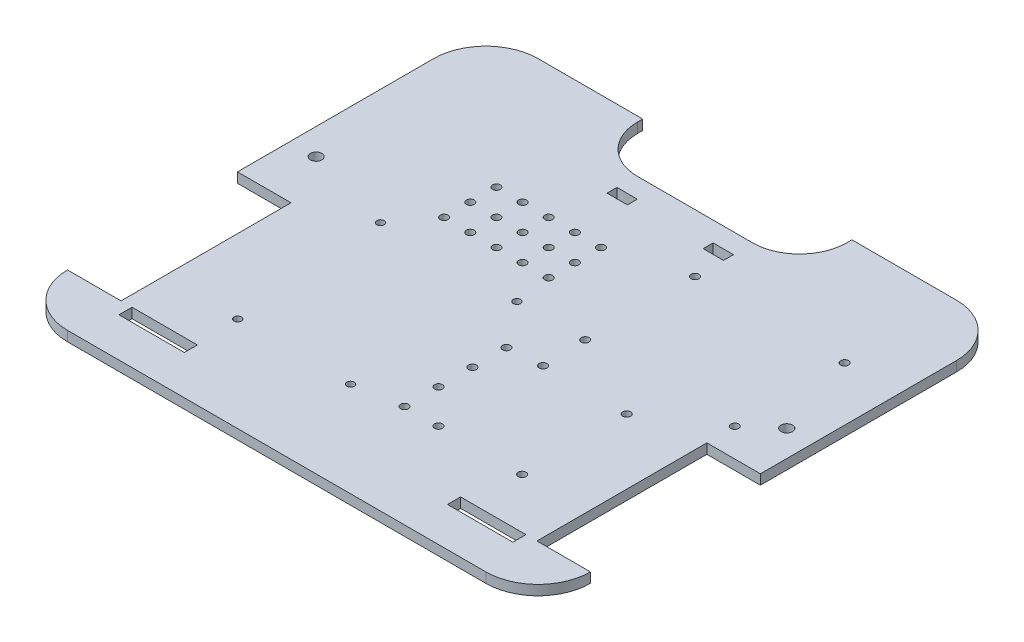
SolidWorks part; units mm, degrees
ref_plane "Front Plane" through (0, 0, 0) normal (0, 0, 1) x (1, 0, 0)
ref_plane "Top Plane" through (0, 0, 0) normal (0, 1, 0) x (1, 0, 0)
ref_plane "Right Plane" through (0, 0, 0) normal (1, 0, 0) x (0, 0, -1)
sketch "Sketch1" plane through (0, 0, 0) normal (0, 1, 0) x (1, 0, 0)
  line L1 (-127, 114.3) -> (127, 114.3)
  line L2 (-127, 114.3) -> (-127, -114.3)
  line L3 (-127, -114.3) -> (127, -114.3)
  line L4 (127, 114.3) -> (127, -114.3)
  line L5 (-127, 114.3) -> (127, -114.3) construction
  line L6 (-127, -114.3) -> (127, 114.3) construction
  point P0 (0, 0)
  dimension "D1" = 254
  dimension "D2" = 228.6
extrude "Boss-Extrude1" add sketch "Sketch1" along normal blind 4.826
sketch "Sketch2" plane through (0, 4.826, 0) normal (0, 1, 0) x (1, 0, 0)
  line L0 (-127, 114.3) -> (-127, -114.3) construction
  line L1 (-127, -6.35) -> (-101, -6.35)
  line L2 (-127, -6.35) -> (-127, -88.9)
  line L3 (-127, -88.9) -> (-101, -88.9)
  line L4 (-101, -6.35) -> (-101, -88.9)
  line L5 (127, -114.3) -> (127, 114.3) construction
  line L6 (127, -6.35) -> (101, -6.35)
  line L7 (127, -6.35) -> (127, -88.9)
  line L8 (127, -88.9) -> (101, -88.9)
  line L9 (101, -6.35) -> (101, -88.9)
  line L10 (-127, -114.3) -> (127, -114.3) construction
  dimension "D1" = 25.4
  dimension "D2" = 25.4
  dimension "D3" = 82.55
  dimension "D4" = 82.55
  dimension "D5" = 26
  dimension "D6" = 26
extrude "Cut-Extrude1" cut sketch "Sketch2" against normal blind 4.826
sketch "Sketch4" plane through (0, 4.826, 0) normal (0, 1, 0) x (1, 0, 0)
  line L0 (0, -114.3) -> (0, 114.3) construction
  line L1 (-127, -114.3) -> (127, -114.3) construction
  line L2 (127, 114.3) -> (-127, 114.3) construction
  line L3 (-127, 88.9) -> (-101.6, 88.9) construction
  line L4 (-127, 114.3) -> (-127, -6.35) construction
  line L5 (-101.6, 88.9) -> (-101.6, 114.3) construction
  line L6 (-127, 88.9) -> (-127, 114.3)
  line L7 (-127, 114.3) -> (-101.6, 114.3)
  line L8 (127, 88.9) -> (127, 114.3)
  line L9 (127, 114.3) -> (101.6, 114.3)
  arc A0 (-127, 88.9) -> (-101.6, 114.3) centre (-101.6, 88.9) cw
  arc A1 (127, 88.9) -> (101.6, 114.3) centre (101.6, 88.9) ccw
extrude "Cut-Extrude3" cut sketch "Sketch4" against normal blind 4.826
sketch "Sketch7" plane through (0, 4.826, 0) normal (0, 1, 0) x (1, 0, 0)
  line L0 (0, -114.3) -> (0, 114.3) construction
  line L1 (-127, -114.3) -> (127, -114.3) construction
  line L2 (101.6, 114.3) -> (-101.6, 114.3) construction
  line L3 (50.8, 88.9) -> (50.8, 114.3)
  line L4 (50.8, 88.9) -> (-50.8, 88.9)
  line L5 (0, 88.9) -> (0, 114.3)
  line L6 (50.8, 114.3) -> (-50.8, 114.3)
  line L7 (-50.8, 88.9) -> (-50.8, 114.3)
  line M6 (101.6, 114.3) -> (-101.6, 114.3)
  dimension "D2" = 50.8
extrude "Cut-Extrude5" cut sketch "Sketch7" against normal blind 4.826 contours L7 L4 L5 M6 | L5 L4 L3 M6 region at (25.4, 4.826, -101.6) region at (-25.4, 4.826, -101.6)
fillet "Fillet9" radius 22.86 1 edges at (-50.8, 2.413, -88.9) type face fillet first side face at (0, 2.413, -88.9) second side face at (-50.8, 2.413, -101.6)
fillet "Fillet10" radius 22.86 1 edges at (50.8, 2.413, -88.9) type face fillet first side face at (11.43, 2.413, -88.9) second side face at (50.8, 2.413, -101.6)
sketch "Sketch8" plane through (0, 4.826, 0) normal (0, 1, 0) x (1, 0, 0)
  line L0 (-127, -88.9) -> (-101.6, -88.9) construction
  line L1 (-101.6, -88.9) -> (-101.6, -114.3) construction
  line L2 (-127, -114.3) -> (127, -114.3) construction
  line L3 (-127, -88.9) -> (-127, -114.3)
  line L4 (-127, -114.3) -> (-101.6, -114.3)
  line L5 (0, -114.3) -> (0, 88.9) construction
  line L6 (27.94, 88.9) -> (-27.94, 88.9) construction
  line L7 (127, -114.3) -> (101.6, -114.3)
  line L8 (127, -88.9) -> (127, -114.3)
  arc A0 (-127, -88.9) -> (-101.6, -114.3) centre (-101.6, -88.9) ccw
  arc A1 (127, -88.9) -> (101.6, -114.3) centre (101.6, -88.9) cw
extrude "Cut-Extrude6" cut sketch "Sketch8" against normal blind 4.826
sketch "Sketch9" plane through (0, 0, 0) normal (0, -1, 0) x (1, 0, 0)
  line L0 (-58.582, 88.9) -> (-101, 88.9) construction
  line L1 (-95.666, 88.9) -> (-63.916, 88.9)
  line L2 (-95.666, 88.9) -> (-95.666, 95.25)
  line L3 (-95.666, 95.25) -> (-63.916, 95.25)
  line L4 (-63.916, 88.9) -> (-63.916, 95.25)
  line L5 (-101, 88.9) -> (-95.666, 88.9) construction
  line L6 (-63.916, 88.9) -> (-58.582, 88.9) construction
  line L7 (0, 114.3) -> (0, -88.9) construction
  line L8 (-101.6, 114.3) -> (101.6, 114.3) construction
  line L9 (27.94, -88.9) -> (-27.94, -88.9) construction
  line L10 (63.916, 88.9) -> (58.582, 88.9) construction
  line L11 (101, 88.9) -> (95.666, 88.9) construction
  line L12 (63.916, 88.9) -> (63.916, 95.25)
  line L13 (95.666, 95.25) -> (63.916, 95.25)
  line L14 (95.666, 88.9) -> (95.666, 95.25)
  line L15 (95.666, 88.9) -> (63.916, 88.9)
  dimension "D1" = 31.75
  dimension "D2" = 6.35
extrude "Cut-Extrude7" cut sketch "Sketch9" against normal through all
sketch "Sketch11" plane through (0, 4.826, 0) normal (0, 1, 0) x (1, 0, 0)
  line L0 (-18.3929, 74.4508) -> (-28.2989, 74.4508) construction
  line L1 (-28.2989, 79.2768) -> (-28.2989, 74.4508) construction
  line L2 (-18.3929, 79.2768) -> (-28.2989, 79.2768) construction
  line L3 (-18.3929, 79.2768) -> (-18.3929, 74.4508) construction
  line L4 (28.2989, 74.4508) -> (18.3929, 74.4508) construction
  line L5 (18.3929, 79.2768) -> (18.3929, 74.4508) construction
  line L6 (28.2989, 79.2768) -> (18.3929, 79.2768) construction
  line L7 (28.2989, 79.2768) -> (28.2989, 74.4508) construction
  line L8 (-18.3929, 74.4508) -> (-28.2989, 74.4508)
  line L9 (-28.2989, 79.2768) -> (-28.2989, 74.4508)
  line L10 (-18.3929, 79.2768) -> (-28.2989, 79.2768)
  line L11 (-18.3929, 79.2768) -> (-18.3929, 74.4508)
  line L12 (28.2989, 74.4508) -> (18.3929, 74.4508)
  line L13 (18.3929, 79.2768) -> (18.3929, 74.4508)
  line L14 (28.2989, 79.2768) -> (18.3929, 79.2768)
  line L15 (28.2989, 79.2768) -> (28.2989, 74.4508)
extrude "Cut-Extrude8" cut sketch "Sketch11" against normal through all
sketch "Sketch13" plane through (0, 4.826, 0) normal (0, 1, 0) x (1, 0, 0)
  line L1 (-0.5324, -70.4824) -> (-0.5324, 9.2736) construction
  circle A0 centre (-6.8824, 24.7159) radius 1.905
  circle A1 centre (-19.5824, 24.7159) radius 1.905
  circle A2 centre (-32.2824, 24.7159) radius 1.905
  circle A3 centre (-44.9824, 24.7159) radius 1.905
  circle A4 centre (-57.6824, 24.7159) radius 1.905
  circle A5 centre (-19.5824, 37.4159) radius 1.905
  circle A6 centre (-32.2824, 37.4159) radius 1.905
  circle A7 centre (-44.9824, 37.4159) radius 1.905
  circle A8 centre (-57.6824, 37.4159) radius 1.905
  circle A9 centre (-19.5824, 50.1159) radius 1.905
  circle A10 centre (-32.2824, 50.1159) radius 1.905
  circle A11 centre (-44.9824, 50.1159) radius 1.905
  circle A12 centre (-57.6824, 50.1159) radius 1.905
  circle A13 centre (-6.8824, 37.4159) radius 1.905
  circle A14 centre (-6.8824, 50.1159) radius 1.905
  dimension "D1" = 3.81
  dimension "D4" = 6.35
  dimension "D2" = 5
  dimension "D3" = 3
extrude "Cut-Extrude10" cut sketch "Sketch13" against normal through all
sketch "Sketch14" plane through (0, 4.826, 0) normal (0, 1, 0) x (1, 0, 0)
  circle A0 centre (-65.0484, -68.1964) radius 1.778 construction
  circle A1 centre (-10.1844, -68.1964) radius 1.778 construction
  circle A2 centre (-70.8904, 6.9876) radius 1.778 construction
  circle A3 centre (-4.5964, 6.9876) radius 1.778 construction
  circle A4 centre (-65.0484, -68.1964) radius 1.778
  circle A5 centre (-10.1844, -68.1964) radius 1.778
  circle A6 centre (-70.8904, 6.9876) radius 1.778
  circle A7 centre (-4.5964, 6.9876) radius 1.778
extrude "Cut-Extrude11" cut sketch "Sketch14" against normal through all
sketch "Sketch15" plane through (0, 4.826, 0) normal (0, 1, 0) x (1, 0, 0)
  circle A0 centre (69.4139, -64.4851) radius 1.905 construction
  circle A1 centre (28.7739, -64.4851) radius 1.905 construction
  circle A2 centre (69.4139, -13.6851) radius 1.905 construction
  circle A3 centre (28.7739, -13.6851) radius 1.905 construction
  circle A4 centre (69.4139, -64.4851) radius 1.905
  circle A5 centre (28.7739, -64.4851) radius 1.905
  circle A6 centre (69.4139, -13.6851) radius 1.905
  circle A7 centre (28.7739, -13.6851) radius 1.905
extrude "Cut-Extrude12" cut sketch "Sketch15" against normal through all
sketch "Sketch16" plane through (0, 4.826, 0) normal (0, 1, 0) x (1, 0, 0)
  circle A0 centre (100.7829, 7.4227) radius 1.905 construction
  circle A1 centre (28.1389, 7.4227) radius 1.905 construction
  circle A2 centre (28.1389, 60.7627) radius 1.905 construction
  circle A3 centre (100.7829, 60.7627) radius 1.905 construction
  circle A4 centre (100.7829, 7.4227) radius 1.905
  circle A5 centre (28.1389, 7.4227) radius 1.905
  circle A6 centre (28.1389, 60.7627) radius 1.905
  circle A7 centre (100.7829, 60.7627) radius 1.905
extrude "Cut-Extrude13" cut sketch "Sketch16" against normal through all
sketch "Sketch17" plane through (0, 0, 0) normal (0, -1, 0) x (1, 0, 0)
  circle A0 centre (114.3, -19.1646) radius 2.7781 construction
  circle A1 centre (-114.3, -19.1646) radius 2.7781 construction
  circle A2 centre (114.3, -19.1646) radius 2.7781
  circle A3 centre (-114.3, -19.1646) radius 2.7781
extrude "Cut-Extrude14" cut sketch "Sketch17" against normal through all
sketch "Sketch18" plane through (0, 4.826, 0) normal (0, 1, 0) x (1, 0, 0)
  circle A0 centre (12.2639, -64.4851) radius 1.905
  circle A1 centre (28.7739, -64.4851) radius 1.905 construction
  circle A2 centre (12.2639, -47.9751) radius 1.905
  circle A3 centre (12.2639, -31.4651) radius 1.905
  circle A4 centre (12.2639, -14.9551) radius 1.905
  dimension "D1" = 3.81
  dimension "D2" = 16.51
  dimension "D3" = 0
  dimension "D4" = 4
extrude "Cut-Extrude15" cut sketch "Sketch18" against normal through all
equation "\"MDF\"= 0.19in"
equation "\"GenDiameter\"= 60mm"
equation "\"GenCutDiameter\" = 1.8in"
equation "\"GenCutDistance\" = 1"
equation "\"TowerHeight\" = 6in"
equation "\"TowerFrontBase\" = 3in"
equation "\"FunnelHeight\" = 1in"
equation "\"FunnelAngle\" = 20"
equation "\"TowerSideBase\" = 3in"
equation "\"BaseLength\" = 9in"
equation "\"BaseWidth\" = 10in"
equation "\"WheelHoleLength\" = 3.25in"
equation "\"WheelHoleWidth\" = 26mm"
equation "\"DropLength\" = 1in"
equation "\"D1@Sketch1\"=\"BaseWidth\""
equation "\"D2@Sketch1\"=\"BaseLength\""
equation "\"D1@Boss-Extrude1\"=\"MDF\""
equation "\"WheelHoleFromBack\" = 1in"
equation "\"D1@Sketch2\"=\"WheelHoleFromBack\""
equation "\"D2@Sketch2\"=\"WheelHoleFromBack\""
equation "\"D3@Sketch2\"=\"WheelHoleLength\""
equation "\"D4@Sketch2\"=\"WheelHoleLength\""
equation "\"D5@Sketch2\"=\"WheelHoleWidth\""
equation "\"D6@Sketch2\"=\"WheelHoleWidth\""
equation "\"D1@Cut-Extrude1\"=\"MDF\""
equation "\"DropWidth\" = 8.5in"
equation "\"BumperWidth\" = 1in"
equation "\"D1@Sketch4\"=\"BumperWidth\""
equation "\"D2@Sketch4\"=\"WheelHoleFromBack\""
equation "\"D1@Cut-Extrude3\"=\"MDF\""
equation "\"D1@Sketch7\"=\"DropLength\""
equation "\"D2@Sketch7\"=\"DropWidthTop\"/2"
equation "\"D1@Cut-Extrude5\"=\"MDF\""
equation "\"D1@Sketch8\"=\"BumperWidth\""
equation "\"D1@Cut-Extrude6\"=\"MDF\""
equation "\"DropWidthTop\" = 4in"
